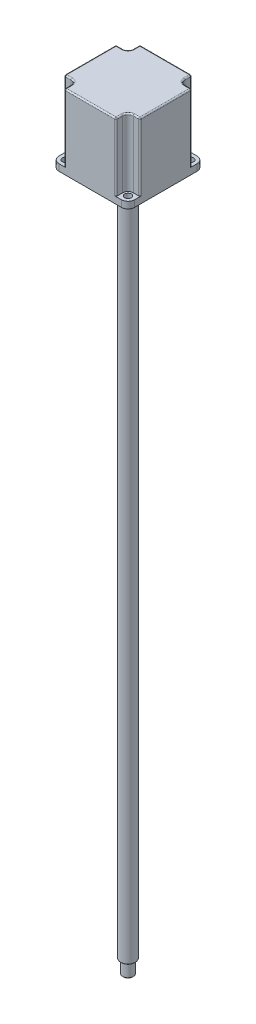
SolidWorks part; units mm, degrees
note: '?' marks a value the reader was unsure of.
material "1023 Carbon Steel Sheet (SS)"
ref_plane "Front" through (0, 0, 0) normal (0, 0, 1) x (1, 0, 0)
ref_plane "Top" through (0, 0, 0) normal (0, 1, 0) x (1, 0, 0)
ref_plane "Right" through (0, 0, 0) normal (1, 0, 0) x (0, 0, -1)
ref_axis "Axis1" through (-84.4107, 0, 0) along (1, 0, 0)?
ref_axis "Axis2" through (0, 64.3378, 0) along (0, -1, 0)?
ref_axis "Axis3" through (0, 0, -102.329) along (0, 0, 1)?
sketch "Sketch1" plane through (0, 0, 0) normal (0, 1, 0) x (1, 0, 0)
  line L1 (-28.5, -28.5) -> (28.5, -28.5)
  line L2 (-28.5, -28.5) -> (-28.5, 28.5)
  line L3 (-28.5, 28.5) -> (28.5, 28.5)
  line L4 (28.5, -28.5) -> (28.5, 28.5)
  line L5 (-28.5, -28.5) -> (28.5, 28.5) construction
  line L6 (-28.5, 28.5) -> (28.5, -28.5) construction
  point P0 (0, 0)
  dimension "D1" = 57
  dimension "D2" = 57
extrude "Extrude1" add sketch "Sketch1" along normal blind 76
hole_wizard "Ø5.0 (5) Diameter Hole1" positions "Sketch5" profile "Sketch4" hole size "Ø5.0" standard "ISO" end condition through all
sketch "Sketch5" plane through (0, 0, 0) normal (0, -1, 0) x (1, 0, 0)
  line L0 (-28.5, 28.5) -> (28.5, -28.5) construction
  line L3 (28.5, 28.5) -> (-28.5, -28.5) construction
  point P0 (-23.5, 23.5)
  point P1 (23.5, 23.5)
  point P3 (23.5, -23.5)
  point P5 (-23.5, -23.5)
  dimension "D1" = 47
  dimension "D2" = 47
sketch "Sketch4" plane through (-23.5, 0, 23.5) normal (1, 0, 0) x (0, 0, -1)
  line L0 (0, 0) -> (0, 76)
  line L1 (0, 76) -> (2.5, 76)
  line L2 (2.5, 76) -> (2.5, 0)
  line L5 (2.5, 0) -> (0, 0)
  line L11 (0, -6.35) -> (0, 107.95) construction
  dimension "Thru Hole Dia." = 5
  dimension "Thru Hole Depth" = 76
sketch "Sketch6" plane through (0, 76, 0) normal (0, 1, 0) x (1, 0, 0)
  line L0 (-19.5, 23.5) -> (-19.5, 32.5117)
  line L1 (-19.5, 32.5117) -> (-33.9089, 32.5117)
  line L2 (-33.9089, 32.5117) -> (-33.9089, 19.5)
  line L3 (-33.9089, 19.5) -> (-23.5, 19.5)
  line L4 (19.5, 23.5) -> (19.5, 36.4716)
  line L5 (19.5, 36.4716) -> (41.1684, 36.4716)
  line L6 (41.1684, 36.4716) -> (41.1684, 19.5)
  line L7 (41.1684, 19.5) -> (23.5, 19.5)
  line L8 (23.5, -19.5) -> (44.2522, -19.5)
  line L9 (44.2522, -19.5) -> (44.2522, -40.0504)
  line L10 (44.2522, -40.0504) -> (19.5, -40.0504)
  line L11 (19.5, -40.0504) -> (19.5, -23.5)
  line L12 (-23.5, -19.5) -> (-37.6708, -19.5)
  line L13 (-37.6708, -19.5) -> (-37.6708, -37.8282)
  line L14 (-37.6708, -37.8282) -> (-19.5, -37.8282)
  line L15 (-19.5, -37.8282) -> (-19.5, -23.5)
  circle A0 centre (-23.5, 23.5) radius 4
  circle A1 centre (23.5, 23.5) radius 4
  circle A2 centre (23.5, -23.5) radius 4
  circle A3 centre (-23.5, -23.5) radius 4
  circle M1 centre (-23.5, -23.5) radius 2.5
  circle M2 centre (23.5, -23.5) radius 2.5
  circle M3 centre (23.5, 23.5) radius 2.5
  circle M4 centre (-23.5, 23.5) radius 2.5
  line M5 (28.5, -28.5) -> (28.5, 28.5)
  line M6 (28.5, 28.5) -> (-28.5, 28.5)
  line M7 (-28.5, 28.5) -> (-28.5, -28.5)
  line M8 (-28.5, -28.5) -> (28.5, -28.5)
  dimension "D1" = 8
  dimension "D2" = 8
  dimension "D3" = 8
  dimension "D4" = 8
extrude "Extrude4" cut sketch "Sketch6" against normal blind 71 contours L2 L3 L0 L1 M7 M6 | A0 L0 L3 M6 M7 | A0 M4 | L7 L6 L5 L4 M6 M5 | A1 L7 L4 M5 M6 | A1 M3 | A2 M2 | A2 L11 L8 M8 M5 | L11 L10 L9 L8 M5 M8 | L14 L15 L12 L13 M8 M7 | A3 L12 L15 M7 M8 | A3 M1
fillet "Fillet1" radius 5 4 edges at (-28.5, 2.5, 28.5) (28.5, 2.5, 28.5) (28.5, 2.5, -28.5) (-28.5, 2.5, -28.5)
sketch "Sketch7" plane through (0, 76, 0) normal (0, 1, 0) x (1, 0, 0)
  circle A0 centre (0, 0) radius 3
  dimension "D1" = 6
extrude "Extrude5" add sketch "Sketch7" against normal blind 101 separate body
sketch "Sketch8" plane through (0, 0, 0) normal (0, -1, 0) x (1, 0, 0)
  circle A0 centre (0, 0) radius 19.05
  dimension "D1" = 38.1
extrude "Extrude6" add sketch "Sketch8" along normal blind 3
fillet "Fillet2" radius 1 24 edges at (-26, 76, 19.5) (-20.6716, 76, 20.6716) (-19.5, 76, 26) (0, 76, 28.5) (19.5, 76, 26) (20.6716, 76, 20.6716) (26, 76, 19.5) (28.5, 76, 0) (19.5, 76, -26) (26, 76, -19.5) (20.6716, 76, -20.6716) (-26, 76, -19.5) (-19.5, 76, -26) (-20.6716, 76, -20.6716) (0, 76, -28.5) (-28.5, 76, 0) (-19.5, 40.5, 28.5) (-28.5, 40.5, 19.5) (-28.5, 40.5, -19.5) (-19.5, 40.5, -28.5) (19.5, 40.5, -28.5) (28.5, 40.5, -19.5) (28.5, 40.5, 19.5) (19.5, 40.5, 28.5)
sketch "Sketch9" plane through (0, 0, 0) normal (0, -1, 0) x (1, 0, 0)
  circle A0 centre (0, 0) radius 5.5
  dimension "D1" = 11
extrude "Boss-Extrude1" add sketch "Sketch9" along normal blind 516
chamfer "Chamfer1" distance 0.5 angle 45 1 edges at (0, -516, -5.5)
sketch "Sketch10" plane through (0, -516, 0) normal (0, -1, 0) x (1, 0, 0)
  circle A0 centre (0, 0) radius 4
  dimension "D1" = 8
extrude "Boss-Extrude2" add sketch "Sketch10" along normal blind 10
chamfer "Chamfer2" distance 0.5 angle 45 1 edges at (0, -526, -4)
sketch "Sketch11" plane through (0, 0, 28.5) normal (0, 0, 1) x (1, 0, 0)
  line L0 (-23.5, 0) -> (23.5, 0) construction
  line L1 (42.7332, 56) -> (-106.5458, 56)
  line L2 (42.7332, 56) -> (42.7332, 147.9775)
  line L3 (42.7332, 147.9775) -> (-106.5458, 147.9775)
  line L4 (-106.5458, 56) -> (-106.5458, 147.9775)
  dimension "D1" = 56
extrude "Cut-Extrude1" cut sketch "Sketch11" against normal up to next
fillet "Fillet3" radius 1 24 edges at (19.2071, 56, 28.2071) (0, 56, 28.5) (-19.2071, 56, 28.2071) (-19.5, 56, 25.5) (-20.6716, 56, 20.6716) (-25.5, 56, 19.5) (-28.2071, 56, 19.2071) (-28.5, 56, 0) (-28.2071, 56, -19.2071) (-25.5, 56, -19.5) (-20.6716, 56, -20.6716) (-19.5, 56, -25.5) (-19.2071, 56, -28.2071) (0, 56, -28.5) (19.2071, 56, -28.2071) (19.5, 56, -25.5) (20.6716, 56, -20.6716) (25.5, 56, -19.5) (28.2071, 56, -19.2071) (28.5, 56, 0) (28.2071, 56, 19.2071) (25.5, 56, 19.5) (20.6716, 56, 20.6716) (19.5, 56, 25.5)
